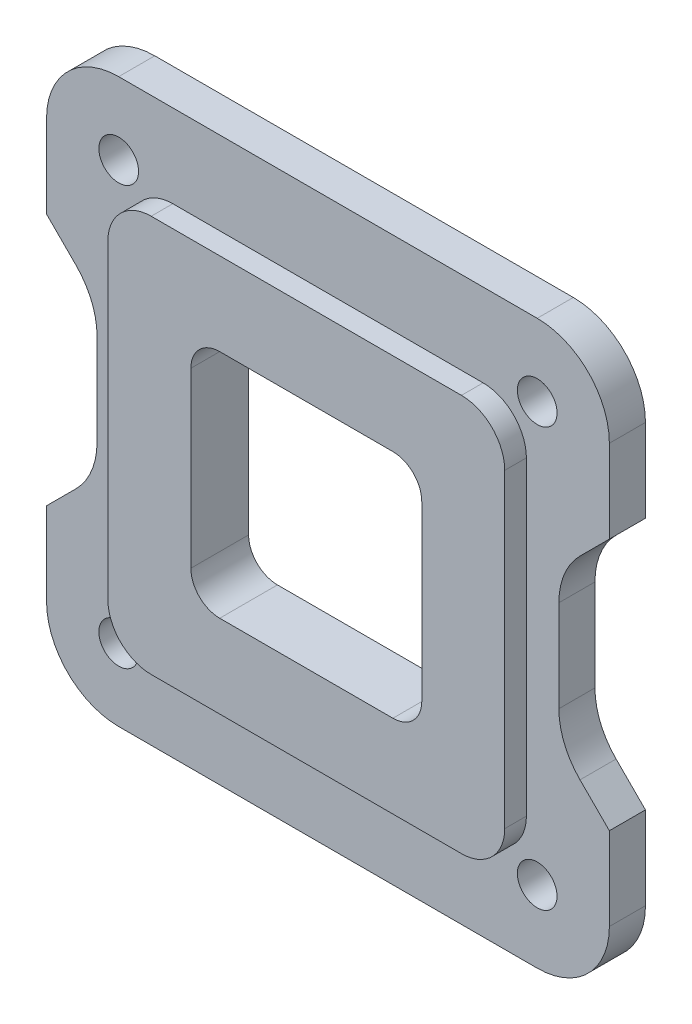
SolidWorks part; units mm, degrees
ref_plane "Front Plane" through (0, 0, 0) normal (0, 0, 1) x (1, 0, 0)
ref_plane "Top Plane" through (0, 0, 0) normal (0, 1, 0) x (1, 0, 0)
ref_plane "Right Plane" through (0, 0, 0) normal (1, 0, 0) x (0, 0, -1)
sketch "Sketch1" plane through (0, 0, 0) normal (0, 0, 1) x (1, 0, 0)
  line L0 (0, -39) -> (0, 39) construction
  line L1 (-29, 39) -> (29, 39)
  line L2 (-39, 29) -> (-39, 17.5)
  line L3 (-29, -39) -> (29, -39)
  line L4 (39, 29) -> (39, 17.5)
  line L5 (-29, -29) -> (-29, 29) construction
  line L6 (-29, 29) -> (29, 29) construction
  line L7 (-39, -17.5) -> (-34.9289, -13.4289)
  line L8 (-32, -6.3579) -> (-32, 6.3579)
  line L9 (0, 21.2748) -> (0, 0) construction
  line L10 (-87.7649, 0) -> (-84.8849, 0) construction
  line L11 (-39, 17.5) -> (-34.9289, 13.4289)
  line L12 (-39, -17.5) -> (-39, -29)
  line L13 (-39, 0) -> (-39, -17.5) construction
  line L14 (-39, 17.5) -> (-39, 0) construction
  line L15 (39, 17.5) -> (34.9289, 13.4289)
  line L16 (32, -6.3579) -> (32, 6.3579)
  line L17 (39, -17.5) -> (34.9289, -13.4289)
  line L18 (39, -17.5) -> (39, -29)
  line L19 (39, 0) -> (39, -17.5) construction
  line L20 (39, 17.5) -> (39, 0) construction
  arc A0 (-39, -29) -> (-29, -39) centre (-29, -29) ccw
  arc A1 (29, -39) -> (39, -29) centre (29, -29) ccw
  arc A2 (39, 29) -> (29, 39) centre (29, 29) ccw
  arc A3 (-29, 39) -> (-39, 29) centre (-29, 29) ccw
  circle A4 centre (-29, 29) radius 2.75
  circle A5 centre (29, 29) radius 2.75
  circle A6 centre (29, -29) radius 2.75
  circle A7 centre (-29, -29) radius 2.75
  arc A8 (34.9289, 13.4289) -> (32, 6.3579) centre (42, 6.3579) ccw
  arc A9 (32, -6.3579) -> (34.9289, -13.4289) centre (42, -6.3579) ccw
  arc A10 (-34.9289, 13.4289) -> (-32, 6.3579) centre (-42, 6.3579) cw
  arc A11 (-32, -6.3579) -> (-34.9289, -13.4289) centre (-42, -6.3579) cw
  point P32 (-32, 0)
  point P41 (32, 10.5)
  point P44 (32, -10.5)
  point P47 (-32, 10.5)
  point P50 (-32, -10.5)
  dimension "D1" = 10
  dimension "D2" = 5.5
  dimension "D7" = 10
  dimension "D3" = 58
  dimension "D4" = 135
  dimension "D5" = 32
  dimension "D6" = 35
extrude "Boss-Extrude1" add sketch "Sketch1" along normal blind 5
sketch "Sketch2" plane through (0, 0, 5) normal (0, 0, -1) x (-1, 0, 0)
  line L0 (0, 27.5) -> (0, -27.5) construction
  line L1 (-21.5, 27.5) -> (21.5, 27.5)
  line L2 (-27.5, 21.5) -> (-27.5, -21.5)
  line L3 (-21.5, -27.5) -> (21.5, -27.5)
  line L4 (27.5, 21.5) -> (27.5, -21.5)
  arc A0 (27.5, 21.5) -> (21.5, 27.5) centre (21.5, 21.5) ccw
  arc A1 (27.5, -21.5) -> (21.5, -27.5) centre (21.5, -21.5) cw
  arc A2 (-27.5, -21.5) -> (-21.5, -27.5) centre (-21.5, -21.5) ccw
  arc A3 (-27.5, 21.5) -> (-21.5, 27.5) centre (-21.5, 21.5) cw
  point P12 (-121.4402, -21.036)
  point P15 (0, 0)
  dimension "D1" = 6
  dimension "D2" = 55
extrude "Boss-Extrude2" add sketch "Sketch2" against normal blind 3
sketch "Sketch3" plane through (0, 0, 0) normal (0, 0, -1) x (-1, 0, 0)
  line L1 (-12, -16) -> (12, -16)
  line L2 (-16, -12) -> (-16, 12)
  line L3 (-12, 16) -> (12, 16)
  line L4 (16, -12) -> (16, 12)
  circle A0 centre (0, 0) radius 16 construction
  arc A1 (-16, -12) -> (-12, -16) centre (-12, -12) ccw
  arc A2 (12, -16) -> (16, -12) centre (12, -12) ccw
  arc A3 (16, 12) -> (12, 16) centre (12, 12) ccw
  arc A4 (-12, 16) -> (-16, 12) centre (-12, 12) ccw
  point P6 (0, 0)
  point P8 (-12.3487, -12.3487)
  dimension "D1" = 32
  dimension "D2" = 4
extrude "Cut-Extrude1" cut sketch "Sketch3" against normal through all both and the other way through all
